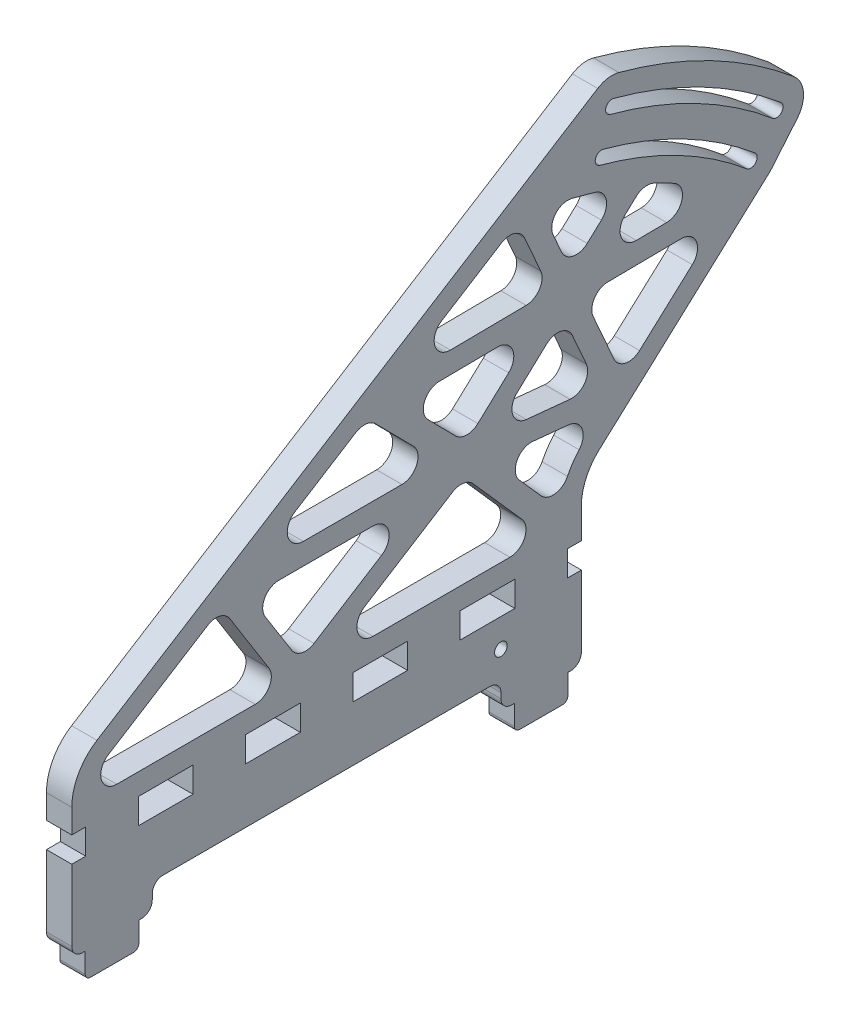
SolidWorks part; units mm, degrees
ref_plane "Front Plane" through (0, 0, 0) normal (0, 0, 1) x (1, 0, 0)
ref_plane "Top Plane" through (0, 0, 0) normal (0, 1, 0) x (1, 0, 0)
ref_plane "Right Plane" through (0, 0, 0) normal (1, 0, 0) x (0, 0, -1)
sketch "DriveBaseGeo"
  dimension "D1" = 6
  dimension "D2" = 6
  dimension "D5" = 203.2
  dimension "D8" = 25.4
  dimension "D9" = 25.4
  dimension "D6" = 9
  dimension "D7" = 9
sketch_block_instance "SlotOutline-1"
sketch_block "SlotOutline" parameters "D1"=12.7, "D2"=6
sketch_block_instance "SlotOutline-2"
sketch_block_instance "SlotOutline-3"
sketch_block_instance "SlotOutline-4"
sketch_block_instance "SlotOutline-5"
sketch_block_instance "SlotOutline-6"
sketch_block_instance "SlotOutline-7"
sketch_block_instance "SlotOutline-8"
sketch_block_instance "SlotOutline-9"
sketch_block_instance "SlotOutline-10"
sketch_block_instance "SlotOutline-11"
sketch_block_instance "SlotOutline-12"
sketch_block_instance "SlotOutline-13"
sketch_block_instance "SlotOutline-14"
sketch_block_instance "SlotOutline-15"
sketch_block_instance "SlotOutline-16"
sketch_block_instance "SlotOutline-17"
sketch_block_instance "SlotOutline-18"
sketch "Sketch2" plane through (0, 0, 0) normal (1, 0, 0) x (0, 0, -1)
  line L0 (-60.325, -47.8) -> (-60.325, -9.7)
  line L1 (-60.325, -9.7) -> (60.325, -9.7)
  line L2 (60.325, -9.7) -> (60.325, -47.8)
  line L3 (60.325, -47.8) -> (57.15, -47.8)
  line L4 (57.15, -47.8) -> (57.15, -53.8) construction
  line L5 (57.15, -53.8) -> (44.45, -53.8) construction
  line L6 (44.45, -53.8) -> (44.45, -47.8) construction
  line L7 (44.45, -47.8) -> (41.275, -47.8)
  line L8 (41.275, -47.8) -> (41.275, -41.45)
  line L9 (41.275, -41.45) -> (-41.275, -41.45)
  line L10 (-41.275, -41.45) -> (-41.275, -47.8)
  line L11 (-41.275, -47.8) -> (-44.45, -47.8)
  line L12 (-44.45, -47.8) -> (-44.45, -53.8) construction
  line L13 (-44.45, -53.8) -> (-57.15, -53.8) construction
  line L14 (-57.15, -53.8) -> (-57.15, -47.8) construction
  line L15 (-57.15, -47.8) -> (-60.325, -47.8)
  line L16 (-57.15, -47.8) -> (-44.45, -53.8) construction
  line L17 (44.45, -47.8) -> (57.15, -53.8) construction
  line L18 (57.15, -47.8) -> (44.45, -53.8) construction
  line L19 (-44.45, -47.8) -> (-57.15, -53.8) construction
  line L20 (101.6, -47.8) -> (-101.6, -47.8) construction
  line L21 (-41.275, -41.45) -> (-60.325, -41.45) construction
  line L22 (41.275, -41.45) -> (60.325, -41.45) construction
  line L23 (-60.325, -50.8) -> (-50.8, -50.8) construction
  line L24 (50.8, -50.8) -> (60.325, -50.8) construction
  line L25 (-57.15, -47.8) -> (-44.45, -47.8)
  line L26 (44.45, -47.8) -> (57.15, -47.8)
  line L27 (101.6, -22.4) -> (-101.6, -22.4) construction
  point P2 (50.8, -50.8)
  point P17 (-50.8, -50.8)
  dimension "D1" = 6.35
  dimension "D2" = 19.05
  dimension "D3" = 101.6
  dimension "D4" = 12.7
  dimension "D5" = 12.7
  dimension "D6" = 6
  dimension "D7" = 9.525
  dimension "D8" = 12.7
extrude "Mounting" add sketch "Sketch2" along normal mid plane 6
sketch "Sketch3" plane through (3, 0, 0) normal (1, 0, 0) x (0, 0, -1)
  line L0 (41.275, -35.1) -> (106.5822, 42.7301) construction
  line L3 (67.571, 63.0381) -> (41.275, -35.1) construction
  line L4 (41.275, -35.1) -> (160.1541, -35.1) construction
  line L6 (101.6, -47.8) -> (-101.6, -47.8) construction
  line L7 (60.325, -9.7) -> (60.325, -47.8) construction
  line L8 (64.1965, 68.4172) -> (-60.325, -9.7)
  line L9 (-60.325, -9.7) -> (60.325, -9.7)
  line L10 (111.4466, 38.6484) -> (105.3241, 31.3518)
  line L11 (105.3241, 31.3518) -> (100.4597, 35.4335) construction
  line L12 (104.7349, 30.7384) -> (60.325, -9.7)
  arc A0 (110.6639, 47.5945) -> (69.2145, 69.1717) centre (41.275, -35.1) ccw
  arc A1 (106.5822, 42.7301) -> (67.571, 63.0381) centre (41.275, -35.1) ccw construction
  arc A2 (107.5464, 43.8792) -> (67.9592, 64.487) centre (41.275, -35.1) ccw
  arc A3 (105.618, 41.581) -> (67.1828, 61.5892) centre (41.275, -35.1) ccw
  arc A4 (105.618, 41.581) -> (107.5464, 43.8792) centre (106.5822, 42.7301) ccw
  arc A5 (67.9592, 64.487) -> (67.1828, 61.5892) centre (67.571, 63.0381) ccw
  arc A6 (110.6639, 47.5945) -> (111.4466, 38.6484) centre (106.5822, 42.7301) cw
  arc A7 (69.2145, 69.1717) -> (64.1965, 68.4172) centre (67.571, 63.0381) ccw
  circle A8 centre (41.275, -35.1) radius 1.5
  arc A9 (100.4597, 35.4335) -> (65.1058, 53.8376) centre (41.275, -35.1) ccw construction
  arc A10 (101.4239, 36.5826) -> (65.494, 55.2865) centre (41.275, -35.1) ccw
  arc A11 (99.4955, 34.2845) -> (64.7175, 52.3887) centre (41.275, -35.1) ccw
  arc A12 (99.4955, 34.2845) -> (101.4239, 36.5826) centre (100.4597, 35.4335) ccw
  arc A13 (65.494, 55.2865) -> (64.7175, 52.3887) centre (65.1058, 53.8376) ccw
  arc A14 (105.3241, 31.3518) -> (104.7349, 30.7384) centre (100.4597, 35.4335) cw
  point P5 (88.1887, 55.0203)
  point P21 (41.275, -35.1)
  point P27 (83.7905, 46.5715)
  dimension "D1" = 3
  dimension "D4" = 6.35
  dimension "D8" = 3
  dimension "D2" = 25
  dimension "D3" = 50
  dimension "D5" = 101.6
  dimension "D6" = 12.7
  dimension "D7" = 19.05
  dimension "D9" = 9.525
extrude "Boss-Extrude2" add sketch "Sketch3" against normal up to surface (6 mm away) up to face at (-3, -36.6875, 0)
extrude "PivotHole" cut sketch "Sketch3<2>" against normal through all both and the other way through all contours A8 region at (3, -35.1, -41.275)
sketch "Sketch3<2>" plane through (3, 0, 0) normal (1, 0, 0) x (0, 0, -1) same geometry as "Sketch3"
sketch "Sketch4" plane through (0, -47.8, 0) normal (0, -1, 0) x (1, 0, 0)
  line L0 (-3, -41.275) -> (-3, -60.325) construction
  line L1 (-3, -60.325) -> (3, -60.325) construction
  line L2 (3, -60.325) -> (3, -41.275) construction
  line L3 (3, -41.275) -> (-3, -41.275) construction
  line L4 (-3, 60.325) -> (-3, 41.275) construction
  line L5 (-3, 41.275) -> (3, 41.275) construction
  line L6 (3, 41.275) -> (3, 60.325) construction
  line L7 (3, 60.325) -> (-3, 60.325) construction
  line L8 (-3, -41.275) -> (-3, -60.325) construction
  line L9 (-3, -60.325) -> (3, -60.325) construction
  line L10 (3, -60.325) -> (3, -41.275) construction
  line L11 (3, -41.275) -> (-3, -41.275) construction
  line L12 (-3, 60.325) -> (-3, 41.275) construction
  line L13 (-3, 41.275) -> (3, 41.275) construction
  line L14 (3, 41.275) -> (3, 60.325) construction
  line L15 (3, 60.325) -> (-3, 60.325) construction
  line L16 (-3, 60.325) -> (3, 41.275) construction
  line L17 (3, 60.325) -> (-3, 41.275) construction
  line L18 (-3, -41.275) -> (3, -60.325) construction
  line L19 (3, -41.275) -> (-3, -60.325) construction
  line L21 (-3, 44.45) -> (3, 44.45)
  line L22 (-3, 44.45) -> (-3, 57.15)
  line L23 (-3, 57.15) -> (3, 57.15)
  line L24 (3, 44.45) -> (3, 57.15)
  line L25 (-3, 44.45) -> (3, 57.15) construction
  line L26 (-3, 57.15) -> (3, 44.45) construction
  line L27 (-3, -57.15) -> (3, -57.15)
  line L28 (-3, -57.15) -> (-3, -44.45)
  line L29 (-3, -44.45) -> (3, -44.45)
  line L30 (3, -57.15) -> (3, -44.45)
  line L31 (-3, -57.15) -> (3, -44.45) construction
  line L32 (-3, -44.45) -> (3, -57.15) construction
  point P6 (0, -50.8)
  point P9 (0, 50.8)
  point P10 (0, 50.8)
  point P15 (0, -50.8)
  dimension "D1" = 12.7
extrude "Tab" add sketch "Sketch4" along normal blind 6
fillet "Fillet1" radius 12.7 2 edges at (0, -9.7, 60.325) (0, -9.7, -60.325)
fillet "Fillet2" radius 2.54 6 edges at (0, -47.8, -60.325) (0, -47.8, -41.275) (0, -41.45, 41.275) (0, -47.8, 41.275) (0, -47.8, 60.325) (0, -41.45, -41.275)
fillet "TabFillet" radius 1.27 4 edges at (0, -53.8, -57.15) (0, -53.8, -44.45) (0, -53.8, 44.45) (0, -53.8, 57.15)
sketch "Sketch5" plane through (3, 0, 0) normal (1, 0, 0) x (0, 0, -1)
  line L0 (101.6, -22.4) -> (-101.6, -22.4) construction
  line L1 (-82.423, -28.4) -> (-95.377, -28.4)
  line L2 (-82.423, -28.4) -> (-82.423, -22.4)
  line L3 (-82.423, -22.4) -> (-95.377, -22.4)
  line L4 (-95.377, -28.4) -> (-95.377, -22.4)
  line L5 (-82.423, -28.4) -> (-95.377, -22.4) construction
  line L6 (-82.423, -22.4) -> (-95.377, -28.4) construction
  line L7 (101.6, -28.4) -> (-101.6, -28.4) construction
  line L8 (-95.25, -28.4) -> (-82.55, -22.4) construction
  line L9 (-57.023, -28.4) -> (-69.977, -28.4)
  line L10 (-57.023, -28.4) -> (-57.023, -22.4)
  line L11 (-69.977, -28.4) -> (-69.977, -22.4)
  line L12 (-57.023, -28.4) -> (-69.977, -22.4) construction
  line L13 (-57.023, -22.4) -> (-69.977, -28.4) construction
  line L14 (-57.023, -22.4) -> (-69.977, -22.4)
  line L15 (-31.623, -28.4) -> (-44.577, -28.4)
  line L16 (-31.623, -28.4) -> (-31.623, -22.4)
  line L17 (-44.577, -28.4) -> (-44.577, -22.4)
  line L18 (-31.623, -28.4) -> (-44.577, -22.4) construction
  line L19 (-31.623, -22.4) -> (-44.577, -28.4) construction
  line L20 (-31.623, -22.4) -> (-44.577, -22.4)
  line L21 (-6.223, -28.4) -> (-19.177, -28.4)
  line L22 (-6.223, -28.4) -> (-6.223, -22.4)
  line L23 (-19.177, -28.4) -> (-19.177, -22.4)
  line L24 (-6.223, -28.4) -> (-19.177, -22.4) construction
  line L25 (-6.223, -22.4) -> (-19.177, -28.4) construction
  line L26 (-6.223, -22.4) -> (-19.177, -22.4)
  line L27 (19.177, -28.4) -> (6.223, -28.4)
  line L28 (19.177, -28.4) -> (19.177, -22.4)
  line L29 (6.223, -28.4) -> (6.223, -22.4)
  line L30 (19.177, -28.4) -> (6.223, -22.4) construction
  line L31 (19.177, -22.4) -> (6.223, -28.4) construction
  line L32 (19.177, -22.4) -> (6.223, -22.4)
  line L33 (44.577, -28.4) -> (31.623, -28.4)
  line L34 (44.577, -28.4) -> (44.577, -22.4)
  line L35 (31.623, -28.4) -> (31.623, -22.4)
  line L36 (44.577, -28.4) -> (31.623, -22.4) construction
  line L37 (44.577, -22.4) -> (31.623, -28.4) construction
  line L38 (44.577, -22.4) -> (31.623, -22.4)
  line L39 (69.977, -28.4) -> (57.023, -28.4)
  line L40 (69.977, -28.4) -> (69.977, -22.4)
  line L41 (57.023, -28.4) -> (57.023, -22.4)
  line L42 (69.977, -28.4) -> (57.023, -22.4) construction
  line L43 (69.977, -22.4) -> (57.023, -28.4) construction
  line L44 (69.977, -22.4) -> (57.023, -22.4)
  line L45 (95.377, -28.4) -> (82.423, -28.4)
  line L46 (95.377, -28.4) -> (95.377, -22.4)
  line L47 (82.423, -28.4) -> (82.423, -22.4)
  line L48 (95.377, -28.4) -> (82.423, -22.4) construction
  line L49 (95.377, -22.4) -> (82.423, -28.4) construction
  line L50 (95.377, -22.4) -> (82.423, -22.4)
  point P0 (-88.9, -25.4)
  point P18 (-63.5, -25.4)
  dimension "D2" = 25.4
  dimension "D3" = 12.446
  dimension "D1" = 8
extrude "Cut-Extrude2" cut sketch "Sketch5" against normal through all both and the other way through all
sketch "Sketch7" plane through (3, 0, 0) normal (1, 0, 0) x (0, 0, -1)
  line L0 (33.0261, 7.8463) -> (72.5595, 44.4656) construction
  line L1 (68.2118, 4.352) -> (47.2733, 51.8037) construction
  line L2 (11.6881, 29.4797) -> (96.2301, 30.393) construction
  line L3 (-24.948, 6.4965) -> (-7.8091, -20.8234)
  line L4 (-7.8091, -20.8234) -> (34.3778, 5.6959)
  line L5 (34.8344, 9.63) -> (17.6972, 27.0045)
  line L6 (17.6972, 27.0045) -> (96.2576, 27.8531)
  line L7 (31.122, 6.1652) -> (53.3409, -19.0011)
  line L8 (64.1304, 7.3098) -> (44.9494, 50.7783)
  line L9 (64.1304, 7.3098) -> (33.2771, 10.3739)
  line L10 (35.0518, 6.2605) -> (76.5725, 44.7206)
  line L11 (-20.6447, 9.1961) -> (-6.2079, -13.8166)
  line L12 (-6.2079, -13.8166) -> (31.6743, 9.9967)
  line L13 (31.2177, 6.0627) -> (5.679, 31.955)
  line L14 (5.679, 31.955) -> (96.2027, 32.9328)
  line L15 (34.9302, 9.5274) -> (57.1491, -15.6389)
  line L16 (72.2933, 1.3942) -> (49.5971, 52.8291)
  line L17 (72.2933, 1.3942) -> (32.7751, 5.3187)
  line L18 (31.3, 9.7097) -> (70.8334, 46.329)
  line L19 (-22.7963, 5.3063) -> (33.0261, 5.3063)
  line L20 (-22.7963, 10.3863) -> (33.0261, 10.3863)
  line L21 (34.7521, 5.9829) -> (74.2855, 42.6021) construction
  line L26 (-55.245, -17.32) -> (55.245, -17.32)
  line L27 (96.2301, 30.393) -> (96.4931, 30.1041)
  line L28 (63.4027, 47.4818) -> (47.2733, 51.8037)
  line L29 (-22.7963, 7.8463) -> (-7.0085, -17.32) construction
  line L30 (-7.0085, -17.32) -> (33.0261, 7.8463) construction
  line L31 (33.0261, 7.8463) -> (55.245, -17.32) construction
  line L32 (-22.7963, 7.8463) -> (33.0261, 7.8463) construction
  line L34 (33.0261, 7.8463) -> (11.6881, 29.4797) construction
  line L37 (68.2118, 4.352) -> (33.0261, 7.8463) construction
  line L52 (-55.245, -16.725) -> (-55.245, -17.32)
  line L53 (-55.245, -17.32) -> (-51.943, -17.32)
  line L54 (-51.943, -17.32) -> (-51.943, -33.48)
  line L55 (-51.943, -33.48) -> (-55.245, -33.48)
  line L56 (-55.245, -33.48) -> (-55.245, -42.72)
  line L57 (-55.245, -42.72) -> (-52.07, -42.72)
  line L58 (-52.07, -42.72) -> (-52.07, -48.72)
  line L59 (-52.07, -48.72) -> (-49.53, -48.72)
  line L60 (-49.53, -48.72) -> (-49.53, -42.72)
  line L61 (-49.53, -42.72) -> (-46.2484, -42.72)
  line L62 (-38.735, -36.37) -> (38.735, -36.37)
  line L63 (46.2484, -42.72) -> (49.53, -42.72)
  line L64 (49.53, -42.72) -> (49.53, -48.72)
  line L65 (49.53, -48.72) -> (52.07, -48.72)
  line L66 (52.07, -48.72) -> (52.07, -42.72)
  line L67 (52.07, -42.72) -> (55.245, -42.72)
  line L68 (55.245, -42.72) -> (55.245, -33.48)
  line L69 (55.245, -33.48) -> (51.943, -33.48)
  line L70 (51.943, -33.48) -> (51.943, -17.32)
  line L71 (51.943, -17.32) -> (55.245, -17.32)
  line L72 (55.245, -17.32) -> (55.245, -15.312)
  line L73 (61.0542, -2.1655) -> (101.3147, 34.4945)
  line L74 (101.4325, 34.6172) -> (107.5551, 41.9138)
  line L75 (66.8961, 64.1139) -> (-51.6744, -10.2701)
  line L76 (-55.245, -16.725) -> (-55.245, -17.32)
  line L96 (55.245, -17.32) -> (55.245, -15.312)
  line L97 (61.0542, -2.1655) -> (101.3147, 34.4945)
  line L98 (101.4325, 34.6172) -> (107.5551, 41.9138)
  line L99 (66.8961, 64.1139) -> (-51.6744, -10.2701)
  arc A19 (96.2301, 30.393) -> (63.4027, 47.4818) centre (41.275, -35.1) ccw
  arc A20 (96.2301, 30.393) -> (63.4027, 47.4818) centre (41.275, -35.1) ccw
  arc A32 (-38.735, -36.37) -> (-46.2484, -42.72) centre (-38.735, -43.99) ccw
  arc A33 (46.2484, -42.72) -> (38.735, -36.37) centre (38.735, -43.99) ccw
  arc A34 (61.0542, -2.1655) -> (55.245, -15.312) centre (73.025, -15.312) ccw
  arc A35 (101.3147, 34.4945) -> (101.4325, 34.6172) centre (100.4597, 35.4335) ccw
  arc A36 (107.5551, 41.9138) -> (107.3986, 43.703) centre (106.5822, 42.7301) ccw
  arc A37 (107.3986, 43.703) -> (67.8997, 64.2648) centre (41.275, -35.1) ccw
  arc A38 (67.8997, 64.2648) -> (66.8961, 64.1139) centre (67.571, 63.0381) ccw
  arc A39 (-51.6744, -10.2701) -> (-55.245, -16.725) centre (-47.625, -16.725) ccw
  arc A42 (61.0542, -2.1655) -> (55.245, -15.312) centre (73.025, -15.312) ccw
  arc A43 (101.3147, 34.4945) -> (101.4325, 34.6172) centre (100.4597, 35.4335) ccw
  arc A44 (107.5551, 41.9138) -> (107.3986, 43.703) centre (106.5822, 42.7301) ccw
  arc A45 (107.3986, 43.703) -> (67.8997, 64.2648) centre (41.275, -35.1) ccw
  arc A46 (67.8997, 64.2648) -> (66.8961, 64.1139) centre (67.571, 63.0381) ccw
  arc A47 (-51.6744, -10.2701) -> (-55.245, -16.725) centre (-47.625, -16.725) ccw
  point P17 (56.9084, 29.9682)
  dimension "D3" = 5.08
  dimension "D4" = 5.08
extrude "Cut-Extrude3" cut sketch "Sketch7" against normal through all both and the other way through all contours L99 A47 L76 L26 L3 | L4 L26 L7 | L13 L99 L20 | L5 L18 L6 | L10 L9 L8 | L19 L11 L12 | A42 L97 L17 L15 | L16 L97 L6 | L8 L99 L14 | L18 A20 L28 L16 | L14 A20 L10 region at (3, -9.1731, 31.7599) region at (3, -10.0309, -27.3905) region at (3, -1.068, 0.0665) region at (3, 16.2899, -5.8966) region at (3, 38.3235, -37.9789) region at (3, -1.8368, -52.6488) region at (3, 21.9147, -33.7183) region at (3, 14.2704, -53.0144) region at (3, 20.4847, -74.9912) region at (3, 43.6194, -59.4101) region at (3, 36.4019, -77.6052)
fillet "Fillet4" radius 3.81 33 edges at (0, 32.8993, -93.0968) (0, 43.3993, -75.1461) (0, 32.5792, -63.4649) (0, 45.4616, -69.897) (0, 50.9601, -50.4218) (0, 34.2514, -57.7947) (0, 50.4396, -45.0989) (0, 32.0644, -15.8081) (0, 32.4665, -53.0297) (0, 6.1554, -70.1924) (0, 27.8287, -93.9942) (0, 27.47, -60.7871) (0, 2.0505, -65.6843) (0, 4.6797, -39.2101) (0, -13.5782, -55.3297) (0, 5.3063, 18.2045) (0, -13.8166, 6.2079) (0, 5.3063, -24.2128) (0, 9.8164, -38.8907) (0, 7.3098, -64.1304) (0, 25.685, -56.0221) (0, 11.3825, -33.1059) (0, 27.3572, -50.3519) (0, 27.0045, -17.6972) (0, 28.0971, -9.4841) (0, 10.3863, 18.7475) (0, 10.3863, -26.9531) (0, -17.32, 2.2359) (0, 4.5472, -32.5505) (0, -17.32, 55.245) (0, -17.32, 10.007) (0, 6.4965, 24.948) (0, -17.32, -51.8567)
equation "\"SlotPitch\"=1"
equation "\"D8@DriveBaseGeo\" = \"SlotPitch\""
equation "\"D9@DriveBaseGeo\" = \"SlotPitch\""
equation "\"D4@Sketch7\"=\"D3@Sketch7\""
